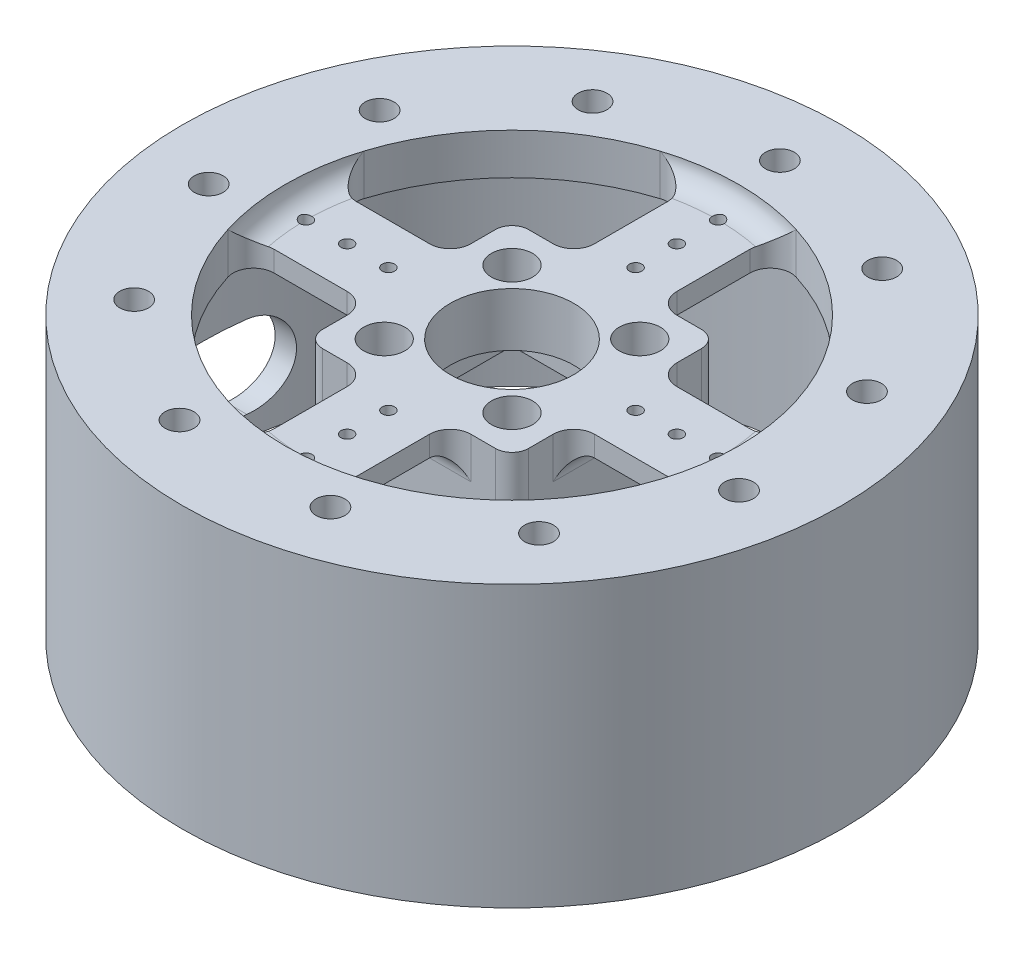
SolidWorks part; units mm, degrees
ref_plane "Front Plane" through (0, 0, 0) normal (0, 0, 1) x (1, 0, 0)
ref_plane "Top Plane" through (0, 0, 0) normal (0, 1, 0) x (1, 0, 0)
ref_plane "Right Plane" through (0, 0, 0) normal (1, 0, 0) x (0, 0, -1)
sketch "Sketch1" plane through (0, 0, 0) normal (0, 1, 0) x (1, 0, 0)
  circle A0 centre (0, 0) radius 80
  dimension "D1" = 160
extrude "Boss-Extrude1" add sketch "Sketch1" along normal blind 10
sketch "Sketch3" plane through (0, 10, 0) normal (0, 1, 0) x (1, 0, 0)
  circle A0 centre (0, 0) radius 65 construction
  circle A1 centre (0, 65) radius 3.5
  circle A2 centre (35.1417, 54.6815) radius 3.5
  circle A3 centre (59.1261, 27.002) radius 3.5
  circle A4 centre (64.3384, -9.2505) radius 3.5
  circle A5 centre (49.1237, -42.5659) radius 3.5
  circle A6 centre (18.3126, -62.367) radius 3.5
  circle A7 centre (-18.3126, -62.367) radius 3.5
  circle A8 centre (-49.1237, -42.5659) radius 3.5
  circle A9 centre (-64.3384, -9.2505) radius 3.5
  circle A10 centre (-59.1261, 27.002) radius 3.5
  circle A11 centre (-35.1417, 54.6815) radius 3.5
  point P27 (0, 0)
  dimension "D1" = 130
  dimension "D2" = 7
  dimension "D3" = 11
extrude "Cut-Extrude1" cut sketch "Sketch3" against normal blind 10
sketch "Sketch5" plane through (0, 10, 0) normal (0, 1, 0) x (1, 0, 0)
  circle A0 centre (0, 0) radius 55
  dimension "D1" = 110
extrude "Cut-Extrude3" cut sketch "Sketch5" against normal blind 21
sketch "Sketch13" plane through (0, 0, 0) normal (0, -1, 0) x (1, 0, 0)
  circle A0 centre (0, -65) radius 7.5
  dimension "D1" = 15
extrude "Cut-Extrude6" cut sketch "Sketch13" against normal blind 3
pattern_circular "CirPattern2" count 11 over 360 about axis through (0, 0, 0) along (0, 1, 0) of "Cut-Extrude6"
sketch "Sketch14" plane through (0, 0, 0) normal (0, -1, 0) x (1, 0, 0)
  line L0 (0, 55) -> (0, 0) construction
  line L1 (0, 0) -> (55, 0) construction
  line L2 (10, 54.0833) -> (10, 10)
  line L3 (10, 10) -> (54.0833, 10)
  line L4 (54.0833, -10) -> (10, -10)
  line L5 (10, -10) -> (10, -54.0833)
  line L6 (-10, -54.0833) -> (-10, -10)
  line L7 (-10, -10) -> (-54.0833, -10)
  line L8 (-54.0833, 10) -> (-10, 10)
  line L9 (-10, 10) -> (-10, 54.0833)
  arc A1 (55, 0) -> (54.0833, 10) centre (0, 0) ccw
  circle A3 centre (0, 0) radius 55 construction
  arc A4 (10, 54.0833) -> (0, 55) centre (0, 0) ccw
  arc A5 (54.0833, -10) -> (55, 0) centre (0, 0) ccw
  arc A6 (0, -55) -> (10, -54.0833) centre (0, 0) ccw
  arc A7 (-10, -54.0833) -> (0, -55) centre (0, 0) ccw
  arc A8 (-55, 0) -> (-54.0833, -10) centre (0, 0) ccw
  arc A9 (-54.0833, 10) -> (-55, 0) centre (0, 0) ccw
  arc A10 (0, 55) -> (-10, 54.0833) centre (0, 0) ccw
  point P27 (0, 0)
  dimension "D1" = 10
  dimension "D2" = 10
  dimension "D3" = 4
extrude "Boss-Extrude4" add sketch "Sketch14" against normal up to surface (10 mm away) contours L3 A1 A5 L4 L5 A6 A7 L6 L7 A8 A9 L8 L9 A10 A4 L2 up to face at (0, 10, 55)
sketch "Sketch16" plane through (0, 10, 0) normal (0, 1, 0) x (1, 0, 0)
  line L1 (-25, 25) -> (25, 25)
  line L2 (-25, 25) -> (-25, -25)
  line L3 (-25, -25) -> (25, -25)
  line L4 (25, 25) -> (25, -25)
  line L5 (-25, 25) -> (25, -25) construction
  line L6 (-25, -25) -> (25, 25) construction
  point P0 (0, 0)
  dimension "D1" = 50
extrude "Boss-Extrude5" add sketch "Sketch16" against normal blind 18
sketch "Sketch17" plane through (0, -8, 0) normal (0, -1, 0) x (1, 0, 0)
  line L1 (-15.5, 15.5) -> (15.5, 15.5) construction
  line L2 (-15.5, 15.5) -> (-15.5, -15.5) construction
  line L3 (-15.5, -15.5) -> (15.5, -15.5) construction
  line L4 (15.5, 15.5) -> (15.5, -15.5) construction
  line L5 (-15.5, 15.5) -> (15.5, -15.5) construction
  line L6 (-15.5, -15.5) -> (15.5, 15.5) construction
  circle A0 centre (-15.5, 15.5) radius 1.5
  circle A1 centre (15.5, 15.5) radius 1.5
  circle A2 centre (15.5, -15.5) radius 1.5
  circle A3 centre (-15.5, -15.5) radius 1.5
  circle A4 centre (0, 0) radius 15
  point P0 (0, 0)
  dimension "D2" = 3
  dimension "D3" = 30
  dimension "D1" = 31
extrude "Cut-Extrude7" cut sketch "Sketch17" against normal through all both and the other way through all
sketch "Sketch18" plane through (0, -8, 0) normal (0, -1, 0) x (1, 0, 0)
  line L0 (-21.5, -21.5) -> (21.5, -21.5)
  line L1 (-15.5, -15.5) -> (15.5, -15.5) construction
  line L2 (-15.5, -15.5) -> (-15.5, 15.5) construction
  line L3 (-15.5, 15.5) -> (15.5, 15.5) construction
  line L4 (15.5, -15.5) -> (15.5, 15.5) construction
  line L5 (-15.5, -15.5) -> (15.5, 15.5) construction
  line L6 (-15.5, 15.5) -> (15.5, -15.5) construction
  line L7 (21.5, -21.5) -> (21.5, 21.5)
  line L8 (-21.5, 21.5) -> (0, 21.5)
  line L9 (-21.5, -21.5) -> (-21.5, 21.5)
  line L14 (25, -25) -> (25, 25)
  line L15 (25, 25) -> (-25, 25)
  line L16 (-25, 25) -> (-25, -25)
  line L17 (-25, -25) -> (25, -25)
  line L18 (25, -25) -> (25, 25)
  line L19 (25, 25) -> (0, 25)
  line L20 (-25, 25) -> (-25, -25)
  line L21 (-25, -25) -> (25, -25)
  line L22 (0, 25) -> (-25, 25)
  line L23 (0, 21.5) -> (21.5, 21.5)
  line L24 (-21.5, 21.5) -> (21.5, 21.5) construction
  line L26 (0, 25) -> (0, 15.5) construction
  point P0 (0, 0)
  dimension "D1" = 6
  dimension "D2" = 0
extrude "Boss-Extrude6" add sketch "Sketch18" along normal blind 50
fillet "Fillet1" radius 5 16 edges at (-10, 5, -25) (-25, 5, -10) (-54.0833, 5, -10) (-10, 5, -54.0833) (10, 5, -54.0833) (54.0833, 5, -10) (10, 5, -25) (25, 5, -10) (25, 5, 10) (10, 5, 25) (-25, 5, 10) (-10, 5, 25) (54.0833, 5, 10) (-54.0833, 5, 10) (-10, 5, 54.0833) (10, 5, 54.0833)
sketch "Sketch19" plane through (0, 0, 0) normal (0, -1, 0) x (1, 0, 0)
  line L0 (0, 25) -> (0, 80) construction
  line L3 (10, 38.8485) -> (-10, 38.8485) construction
  line L4 (10, 47.697) -> (10, 30) construction
  line L5 (-10, 30) -> (-10, 47.697) construction
  line L6 (25, 25) -> (-25, 25) construction
  line L9 (30, 0) -> (50, 0) construction
  circle A10 centre (0, 0) radius 80 construction
  circle A11 centre (0, 30) radius 1.5
  circle A12 centre (0, 40) radius 1.5
  circle A13 centre (0, 50) radius 1.5
  circle A14 centre (50, 0) radius 1.5
  circle A15 centre (40, 0) radius 1.5
  circle A16 centre (30, 0) radius 1.5
  circle A17 centre (0, -50) radius 1.5
  circle A18 centre (0, -40) radius 1.5
  circle A19 centre (0, -30) radius 1.5
  circle A20 centre (-50, 0) radius 1.5
  circle A21 centre (-40, 0) radius 1.5
  circle A22 centre (-30, 0) radius 1.5
  point P15 (38.8485, 0)
  point P38 (0, 0)
  point P48 (0, 0)
  dimension "D2" = 3
  dimension "D1" = 5
  dimension "D4" = 10
  dimension "D3" = 3
  dimension "D5" = 4
extrude "Cut-Extrude8" cut sketch "Sketch19" against normal through all both and the other way through all
fillet "Fillet2" radius 5 4 edges at (0, 0, 25) (0, 0, -25) (25, 0, 0) (-25, 0, 0)
sketch "Sketch21" plane through (0, 10, 0) normal (0, 1, 0) x (1, 0, 0)
  circle A0 centre (15.5, 15.5) radius 5
  circle A1 centre (15.5, -15.5) radius 5
  circle A2 centre (-15.5, -15.5) radius 5
  circle A3 centre (-15.5, 15.5) radius 5
  dimension "D1" = 10
extrude "Cut-Extrude10" cut sketch "Sketch21" against normal blind 15
fillet "Fillet3" radius 2 4 edges at (21.5, -33, 21.5) (21.5, -33, -21.5) (-21.5, -33, -21.5) (-21.5, -33, 21.5)
fillet "Fillet4" radius 4 4 edges at (-25, -24, 25) (-25, -24, -25) (25, -24, -25) (25, -24, 25)
sketch "Sketch23" plane through (0, -58, 0) normal (0, -1, 0) x (1, 0, 0)
  line L0 (19.5, 21.5) -> (-19.5, 21.5) construction
  line L1 (-10, 18) -> (10, 18)
  line L2 (-10, 18) -> (-10, 25)
  line L3 (-10, 25) -> (10, 25)
  line L4 (10, 18) -> (10, 25)
  line L5 (-10, 18) -> (10, 25) construction
  line L6 (-10, 25) -> (10, 18) construction
  line L7 (15, 25) -> (-15, 25) construction
  point P0 (0, 21.5)
  dimension "D1" = 20
extrude "Cut-Extrude11" cut sketch "Sketch23" against normal blind 15
fillet "Fillet7" radius 2.5 4 edges at (10, -58, 23.25) (-10, -58, 23.25) (-10, -43, 23.25) (10, -43, 23.25)
pattern_circular "CirPattern3" count 4 over 360 about axis through (0, 0, 0) along (0, 1, 0) of "Cut-Extrude11", "Fillet7"
sketch "Sketch24" plane through (0, 10, 0) normal (0, 1, 0) x (1, 0, 0)
  circle A0 centre (0, 0) radius 55
  arc A1 (52.4667, 16.5) -> (16.5, 52.4667) centre (0, 0) ccw construction
extrude "Cut-Extrude12" cut sketch "Sketch24" against normal blind 5
fillet "Fillet8" radius 5 4 edges at (-55, 5, 0) (0, 5, 55) (55, 5, 0) (0, 5, -55)
sketch "Sketch25" plane through (0, 0, 0) normal (1, 0, 0) x (0, 0, -1)
  line L0 (10, -50.5) -> (-10, -50.5) construction
  line L1 (10, -45.5) -> (10, -55.5) construction
  line L2 (-10, -45.5) -> (-10, -55.5) construction
  line L3 (17.5, -50.5) -> (17.5, -58) construction
  line L4 (21, -58) -> (12.5, -58) construction
  line L5 (10, -50.5) -> (25, -50.5) construction
  line L6 (25, 5) -> (25, -58) construction
  line L7 (0, -50.5) -> (0, -43) construction
  line L8 (7.5, -43) -> (-7.5, -43) construction
  circle A0 centre (17.5, -50.5) radius 1.5
  circle A1 centre (-17.5, -50.5) radius 1.5
  dimension "D1" = 3
extrude "Cut-Extrude13" cut sketch "Sketch25" against normal through all both and the other way through all
sketch "Sketch27" plane through (0, -58, 0) normal (0, -1, 0) x (1, 0, 0)
  circle A0 centre (0, 0) radius 80
  circle A1 centre (0, 0) radius 75
  circle A2 centre (0, 0) radius 80 construction
  dimension "D1" = 5
extrude "Boss-Extrude7" add sketch "Sketch27" against normal up to surface (58 mm away) up to face at (-50, 0, 1.5)
sketch "Sketch28" plane through (0, -58, 0) normal (0, -1, 0) x (1, 0, 0)
  line L0 (21, 25) -> (12.5, 25) construction
  line L1 (-25, -25) -> (25, -25)
  line L2 (-25, -25) -> (-25, 25)
  line L3 (-25, 25) -> (25, 25)
  line L4 (25, -25) -> (25, 25)
  line L5 (-25, -25) -> (25, 25) construction
  line L6 (-25, 25) -> (25, -25) construction
  line L7 (25, -15) -> (25, 15) construction
  point P0 (0, 0)
extrude "Cut-Extrude14" cut sketch "Sketch28" against normal blind 40
sketch "Sketch29" plane through (0, 0, 0) normal (1, 0, 0) x (0, 0, -1)
  line L0 (0, 10) -> (0, -58) construction
  line L1 (16.5, 10) -> (-16.5, 10) construction
  line L2 (-80, -58) -> (80, -58) construction
  line L3 (-10, -43) -> (10, -43) construction
  line L4 (-10, -33) -> (10, -33)
  line L5 (-10, -53) -> (10, -53)
  arc A0 (-10, -33) -> (-10, -53) centre (-10, -43) ccw
  arc A1 (10, -53) -> (10, -33) centre (10, -43) ccw
  point P8 (0, -43)
  dimension "D2" = 10
  dimension "D1" = 15
  dimension "D3" = 20
extrude "Cut-Extrude15" cut sketch "Sketch29" against normal blind 111
